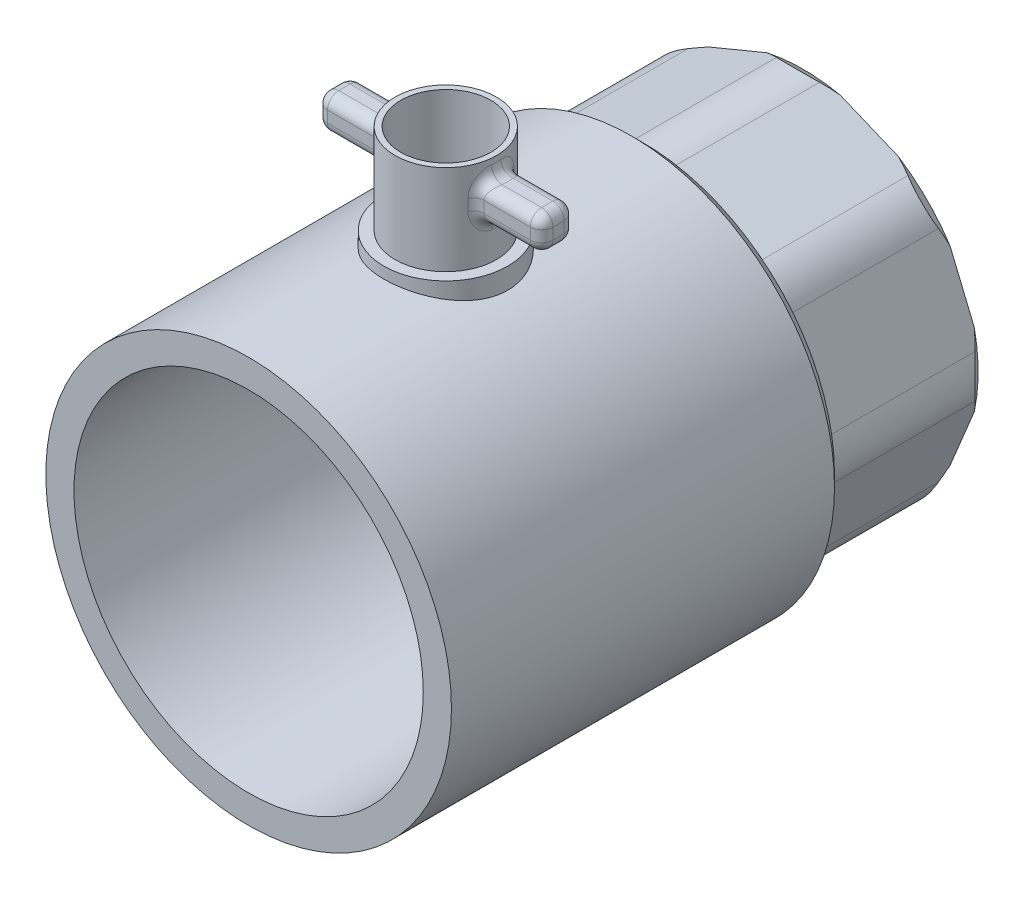
SolidWorks part; units mm, degrees
ref_plane "Płaszczyzna przednia" through (0, 0, 0) normal (0, 0, 1) x (1, 0, 0)
ref_plane "Płaszczyzna górna" through (0, 0, 0) normal (0, 1, 0) x (1, 0, 0)
ref_plane "Płaszczyzna prawa" through (0, 0, 0) normal (1, 0, 0) x (0, 0, -1)
sketch "Szkic1" plane through (0, 0, 0) normal (0, 0, 1) x (1, 0, 0)
  circle A0 centre (0, 0) radius 33
  dimension "D1" = 66
extrude "Dodanie-wyciągnięcie1" add sketch "Szkic1" along normal blind 28.5
sketch "Szkic2" plane through (0, 0, 28.5) normal (0, 0, 1) x (1, 0, 0)
  circle A0 centre (0, 0) radius 36
  point P0 (0, 0)
  dimension "D1" = 72
extrude "Dodanie-wyciągnięcie2" add sketch "Szkic2" along normal blind 70
sketch "Szkic5" plane through (0, 0, 0) normal (0, 1, 0) x (1, 0, 0)
  circle A0 centre (0, -63.5) radius 11
extrude "Dodanie-wyciągnięcie4" add sketch "Szkic5" along normal blind 38
sketch "Szkic6" plane through (0, 38, 0) normal (0, 1, 0) x (1, 0, 0)
  circle A0 centre (0, -63.5) radius 9
  dimension "D1" = 18
extrude "Dodanie-wyciągnięcie5" add sketch "Szkic6" along normal blind 16
sketch "Szkic7" plane through (0, 54, 0) normal (0, 1, 0) x (1, 0, 0)
  circle A0 centre (0, -63.5) radius 8
  dimension "D1" = 16
extrude "Wytnij-wyciągnięcie1" cut sketch "Szkic7" against normal blind 47
sketch "Szkic8" plane through (0, 0, 0) normal (1, 0, 0) x (0, 0, -1)
  line L5 (-66.5, 45) -> (-60.5, 45)
  line L6 (-66.5, 45) -> (-66.5, 51)
  line L7 (-66.5, 51) -> (-60.5, 51)
  line L8 (-60.5, 45) -> (-60.5, 51)
  line L9 (-66.5, 45) -> (-60.5, 51) construction
  line L10 (-66.5, 51) -> (-60.5, 45) construction
  dimension "D2" = 6
  dimension "D3" = 6
extrude "Dodanie-wyciągnięcie6" add sketch "Szkic8" along normal mid plane 40
fillet "Zaokrąglenie3" radius 2 12 edges at (9, 45, 63.5) (9, 51, 63.5) (20, 48, 60.5) (14.2426, 51, 60.5) (8.4853, 48, 60.5) (14.2426, 45, 60.5) (20, 48, 66.5) (14.2426, 45, 66.5) (8.4853, 48, 66.5) (14.2426, 51, 66.5) (20, 45, 63.5) (20, 51, 63.5)
fillet "Zaokrąglenie4" radius 2 12 edges at (-8.4853, 48, 66.5) (-14.2426, 45, 66.5) (-14.2426, 45, 60.5) (-14.2426, 51, 60.5) (-8.4853, 48, 60.5) (-20, 48, 60.5) (-20, 48, 66.5) (-20, 45, 63.5) (-9, 45, 63.5) (-9, 51, 63.5) (-20, 51, 63.5) (-14.2426, 51, 66.5)
sketch "Szkic9" plane through (0, 51, 0) normal (0, 1, 0) x (1, 0, 0)
  circle A0 centre (0, -63.5) radius 8
extrude "Wytnij-wyciągnięcie2" cut sketch "Szkic9" against normal blind 30
sketch "Szkic11" plane through (0, 0, 0) normal (0, 0, -1) x (-1, 0, 0)
  line L1 (0, 33) -> (-23.3345, 23.3345)
  line L2 (-23.3345, 23.3345) -> (-33, 0)
  line L3 (-33, 0) -> (-23.3345, -23.3345)
  line L4 (-23.3345, -23.3345) -> (0, -33)
  line L5 (0, -33) -> (23.3345, -23.3345)
  line L6 (23.3345, -23.3345) -> (33, 0)
  line L7 (33, 0) -> (23.3345, 23.3345)
  line L8 (23.3345, 23.3345) -> (0, 33)
  circle A8 centre (0, 0) radius 30.488 construction
  circle A9 centre (0, 0) radius 33
  point P22 (0, 0)
  circle M1 centre (0, 0) radius 33
sketch "Szkic13" plane through (0, 0, 0) normal (0, 0, -1) x (-1, 0, 0)
  circle A0 centre (0, 0) radius 28.35
  dimension "D1" = 56.7
extrude "Wytnij-wyciągnięcie4" cut sketch "Szkic13" against normal blind 27.5
sketch "Szkic14" plane through (0, 0, 27.5) normal (0, 0, -1) x (-1, 0, 0)
  circle A0 centre (0, 0) radius 25
  dimension "D1" = 50
extrude "Wytnij-wyciągnięcie5" cut sketch "Szkic14" against normal blind 5
sketch "Szkic17" plane through (0, 0, 32.5) normal (0, 0, -1) x (-1, 0, 0)
  circle A0 centre (0, 0) radius 27.5
  dimension "D1" = 55
extrude "Wytnij-wyciągnięcie6" cut sketch "Szkic17" against normal through all
sketch "Szkic20" plane through (0, 0, 98.5) normal (0, 0, 1) x (1, 0, 0)
  circle A0 centre (0, 0) radius 31
  dimension "D1" = 62
extrude "Wytnij-wyciągnięcie7" cut sketch "Szkic20" against normal blind 50
chamfer "Sfazowanie2" distance 2 angle 45 1 edges at (36, 0, 28.5)
chamfer "Sfazowanie3" distance 1 angle 45 1 edges at (-28.35, 0, 0)
cosmetic thread "Oznaczenie gwintu1" parameters "D2"=56.71
extrude "Wytnij-wyciągnięcie8" cut sketch "Szkic11" against normal blind 28.5 contours L2 M1 | L1 M1 | L8 M1 | L3 M1 | L4 M1 | L5 M1 | L6 M1 | L7 M1 region at (-12.0531, 29.0987, 0) region at (12.0531, 29.0987, 0) region at (29.0987, 12.0531, 0) region at (-29.0987, 12.0531, 0) region at (29.0987, -12.0531, 0) region at (-29.0987, -12.0531, 0) region at (12.0531, -29.0987, 0) region at (-12.0531, -29.0987, 0)
sketch "Szkic21" plane through (0, 0, 0) normal (1, 0, 0) x (0, 0, -1)
  line L0 (0, 33) -> (-3, 33)
  line L1 (-28.5, 33) -> (0, 33) construction
  line L2 (-3, 33) -> (0, 31)
  line L3 (0, 33) -> (0, 23.3345) construction
  line L4 (0, 31) -> (0, 33)
  line L5 (0, 0) -> (-19.0331, 0) construction
  line L6 (-28.5, 0) -> (0, 0) construction
  dimension "D1" = 2
  dimension "D2" = 3
revolve "Wycięcie-obrót1" cut sketch "Szkic21" angle 360 about L5
fillet "Zaokrąglenie5" radius 10 8 edges at (-23.3345, -23.3345, 15.75) (0, -33, 15.75) (-33, 0, 15.75) (-23.3345, 23.3345, 15.75) (0, 33, 15.75) (23.3345, -23.3345, 15.75) (33, 0, 15.75) (23.3345, 23.3345, 15.75)
sketch "Szkic22" plane through (0, 0, 48.5) normal (0, 0, 1) x (1, 0, 0)
  circle A0 centre (0, 0) radius 28.5
  dimension "D1" = 57
extrude "Wytnij-wyciągnięcie9" cut sketch "Szkic22" against normal blind 4
sketch "Szkic23" plane through (0, 0, 0) normal (0, 1, 0) x (1, 0, 0)
  circle A0 centre (0, -63.5) radius 11
extrude "Wytnij-wyciągnięcie10" cut sketch "Szkic23" along normal blind 34
